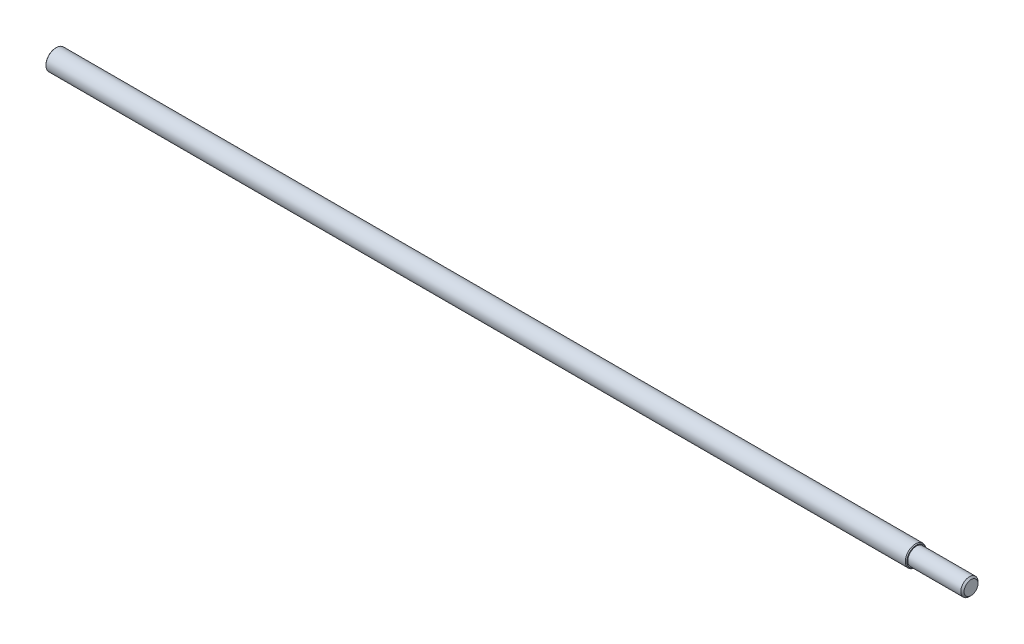
SolidWorks part; units mm, degrees
ref_plane "Front Plane" through (0, 0, 0) normal (0, 0, 1) x (1, 0, 0)
ref_plane "Top Plane" through (0, 0, 0) normal (0, 1, 0) x (1, 0, 0)
ref_plane "Right Plane" through (0, 0, 0) normal (1, 0, 0) x (0, 0, -1)
sketch "Sketch1" plane through (0, 0, 0) normal (1, 0, 0) x (0, 0, -1)
  circle A0 centre (0, 0) radius 4.7625 construction
  circle A2 centre (0, 0) radius 4.7879 construction
  dimension "Diameter" = 9.525
  dimension "Finish Thickness" = 0.0254
sketch "Sketch2" plane through (0, 0, 0) normal (0, 0, 1) x (1, 0, 0)
  line L0 (0, 0) -> (304.8, 0) construction
  line L1 (0, 0) -> (-304.8, 0) construction
  line L2 (304.8, 0) -> (304.8, 4.7625) construction
  line L3 (304.8, 0) -> (304.8, -4.7625) construction
  line L4 (304.8, 4.7625) -> (0, 4.7625) construction
  line L7 (0, 4.7625) -> (-304.8, 4.7625) construction
  line L8 (-304.8, 4.7625) -> (-304.8, 0) construction
  point P5 (-254, 0)
  point P8 (254, 0)
  dimension "Length" = 609.6
  dimension "D1" = 50.8
  dimension "D2" = 50.8
sketch "Sketch4" plane through (0, 0, 0) normal (1, 0, 0) x (0, 0, -1)
  circle A0 centre (0, 0) radius 4.7625 construction
  circle A1 centre (0, 0) radius 4.7625
extrude "Boss-Extrude1" add sketch "Sketch4" along normal up to vertex (304.8 mm away) and the other way up to vertex (304.8 mm away) up to point (304.8, 0, 0) other way up to point (-304.8, 0, 0)
chamfer "Chamfer1" distance 0.2476 angle 45 2 edges at (-304.8, 0, -4.7625) (304.8, 0, -4.7625)
sketch "Sketch5" plane through (0, 0, 0) normal (0, 0, 1) x (1, 0, 0)
  line L0 (304.8, 0) -> (120.65, 0)
  line L1 (304.8, -4.5149) -> (304.8, 4.5149) construction
  line L2 (120.65, 0) -> (120.65, 3.238)
  line L3 (120.65, 3.238) -> (119.888, 4)
  line L4 (119.888, 4) -> (95.25, 4)
  line L5 (95.25, 4) -> (95.25, 4.3815)
  line L6 (95.25, 4.3815) -> (94.869, 4.7625)
  line L7 (304.5524, 4.7625) -> (-304.5523, 4.7625) construction
  line L8 (94.869, 4.7625) -> (304.8, 4.7625)
  line L9 (304.8, 4.7625) -> (304.8, 0)
  line L10 (120.65, 0) -> (239.2618, 0) construction
  line L11 (-304.8, 4.5148) -> (-304.8, -4.5148) construction
  dimension "D1" = 8
  dimension "D2" = 425.45
  dimension "D3" = 45
  dimension "D4" = 0.762
  dimension "D5" = 0.381
  dimension "D6" = 45
  dimension "D7" = 25.4
revolve "Cut-Revolve1" cut sketch "Sketch5" angle 360 about L10
equation "\"D1@Chamfer1\" = \"Diameter@Sketch1\" * .026"
equation "\"D2@Sketch2\" = \"D1@Sketch2\""
